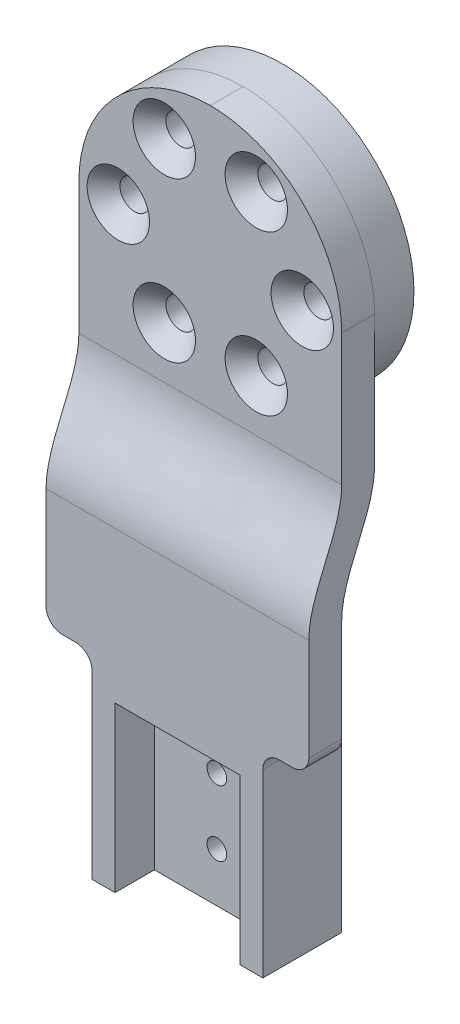
SolidWorks part; units mm, degrees
other "Markup1"
sketch "Sketch13" plane through (20, -53, 11) normal (0.0614, -0.6805, 0.7302) x (0.9699, -0.1321, -0.2046)
ref_plane "Front Plane" through (0, 0, 0) normal (0, 0, 1) x (1, 0, 0)
ref_plane "Top Plane" through (0, 0, 0) normal (0, 1, 0) x (1, 0, 0)
ref_plane "Right Plane" through (0, 0, 0) normal (1, 0, 0) x (0, 0, -1)
sketch "Sketch7" plane through (0, 0, 0) normal (0, 0, 1) x (1, 0, 0)
  line L1 (-20, 20) -> (20, 20)
  line L2 (-20, 20) -> (-20, -20)
  line L3 (-20, -20) -> (20, -20)
  line L4 (20, 20) -> (20, -20)
  line L5 (-20, 20) -> (20, -20) construction
  line L6 (-20, -20) -> (20, 20) construction
  point P0 (0, 0)
extrude "Boss-Extrude1" add sketch "Sketch7" along normal blind 11
ref_plane "Plane2" through (0, -21.4103, 5.7369) normal (0, -0.9659, 0.2588) x (1, 0, 0)
sketch "Sketch8" plane through (0, -20, 2.0782) normal (0, -1, 0) x (1, 0, 0)
  line L0 (20, 8.9218) -> (20, -2.0782) construction
  line L1 (-20, 8.9218) -> (20, 8.9218)
  line L2 (-20, 8.9218) -> (-20, 3.9218)
  line L3 (-20, 3.9218) -> (20, 3.9218)
  line L4 (20, 8.9218) -> (20, 3.9218)
  line L5 (0, 3.9218) -> (0, 8.9218) construction
  line L6 (-20, 6.4218) -> (20, 6.4218) construction
  line L7 (-20, -2.0782) -> (20, -2.0782) construction
  point P764 (0, 6.4218)
  dimension "D1" = 6
ref_plane "Plane4" through (0, -38, 0) normal (0, -1, 0) x (-1, 0, 0)
sketch "Sketch19" plane through (0, -38, 0) normal (0, -1, 0) x (-1, 0, 0)
  line L0 (20, -11) -> (20, 0) construction
  line L1 (20, -16) -> (-20, -16)
  line L2 (20, -16) -> (20, -11)
  line L3 (20, -11) -> (-20, -11)
  line L4 (-20, -16) -> (-20, -11)
  line L5 (20, -16) -> (-20, -11) construction
  line L6 (20, -11) -> (-20, -16) construction
  line L7 (-20, -11) -> (-20, 0) construction
  line L8 (20, -11) -> (-20, -11) construction
  point P4 (0, -13.5)
  dimension "D1" = 5
  dimension "D2" = 5
loft "Loft1" add profiles "Sketch19", "Sketch8" start constraint normal to profile start tangent length 1 end constraint normal to profile end tangent length 1 connector at (-20, -38, 16) connector at (-20, -20, 11)
sketch "Sketch16" plane through (0, 0, 0) normal (0, 0, -1) x (-1, 0, 0)
  line L1 (24.5131, 32.6211) -> (-24.5131, 32.6211)
  line L2 (24.5131, 32.6211) -> (24.5131, -32.6211)
  line L3 (24.5131, -32.6211) -> (-24.5131, -32.6211)
  line L4 (-24.5131, 32.6211) -> (-24.5131, -32.6211)
  line L5 (24.5131, 32.6211) -> (-24.5131, -32.6211) construction
  line L6 (24.5131, -32.6211) -> (-24.5131, 32.6211) construction
  circle A0 centre (0, 0) radius 20
extrude "Cut-Extrude3" cut sketch "Sketch16" against normal blind 6
ref_plane "Plane3" [suppressed] through (0, -56, 0) normal (0, -1, 0) x (-1, 0, 0)
sketch "Sketch17" plane through (0, -38, 0) normal (0, -1, 0) x (-1, 0, 0)
  line L1 (20, -16) -> (-20, -16)
  line L2 (20, -16) -> (20, -11)
  line L3 (20, -11) -> (-20, -11)
  line L4 (-20, -16) -> (-20, -11)
  line L5 (20, -16) -> (-20, -11) construction
  line L6 (20, -11) -> (-20, -16) construction
  line L10 (-20, -16) -> (20, -16) construction
  line L11 (-20, -6) -> (-20, -11) construction
  line L12 (20, -11) -> (20, -6) construction
  point P4 (0, -13.5)
  dimension "D1" = 5
extrude "Boss-Extrude5" add sketch "Sketch17" along normal blind 18
sketch "Sketch10" plane through (0, 0, 11) normal (0, 0, 1) x (1, 0, 0)
  circle A0 centre (-7.0001, 12.1244) radius 2.25
  circle A1 centre (6.9999, 12.1244) radius 2.25
  circle A2 centre (13.9999, 0.0001) radius 2.25
  circle A3 centre (6.9999, -12.1243) radius 2.25
  circle A4 centre (-7.0001, -12.1243) radius 2.25
  circle A5 centre (-14.0001, 0.0001) radius 2.25
  point P0 (0, 0)
  point P1 (0.0025, 0.0011)
  dimension "D4" = 4.5
extrude "Cut-Extrude1" cut sketch "Sketch10" against normal blind 25
sketch "Sketch11" plane through (0, -56, -3.473) normal (0, 1, 0) x (1, 0, 0)
  line L0 (20, -19.473) -> (-20, -19.473) construction
  line L5 (13, -7.473) -> (-13, -7.473)
  line L6 (13, -7.473) -> (13, -19.473)
  line L7 (13, -19.473) -> (-13, -19.473)
  line L8 (-13, -7.473) -> (-13, -19.473)
  line L9 (13, -7.473) -> (-13, -19.473) construction
  line L10 (13, -19.473) -> (-13, -7.473) construction
  line L12 (-20, -19.473) -> (-20, -14.473) construction
  point P0 (0, -13.473)
  dimension "D1" = 26
  dimension "D2" = 20
  dimension "D3" = 12
chamfer "Chamfer1" distance 2.5 angle 45 6 edges at (-4.7501, 12.1244, 11) (-11.7501, 0.0001, 11) (-4.7501, -12.1243, 11) (9.2499, 12.1244, 11) (16.2499, 0.0001, 11) (9.2499, -12.1243, 11)
fillet "Fillet3" radius 20 2 edges at (20, 20, 8.5) (-20, 20, 8.5)
extrude "Boss-Extrude6" add sketch "Sketch11" against normal blind 30
ref_plane "Plane5" through (0, -86, 0) normal (0, -1, 0) x (-1, 0, 0)
sketch "Sketch21" plane through (0, -86, 0) normal (0, -1, 0) x (-1, 0, 0)
  line L0 (13, -16) -> (-13, -16) construction
  line L1 (-9.5, -10) -> (9.5, -10)
  line L2 (-9.5, -10) -> (-9.5, -16)
  line L3 (-9.5, -16) -> (9.5, -16)
  line L4 (9.5, -10) -> (9.5, -16)
  line L5 (-9.5, -10) -> (9.5, -16) construction
  line L6 (-9.5, -16) -> (9.5, -10) construction
  line L7 (13, -4) -> (13, -16) construction
  point P0 (0, -13)
  dimension "D1" = 6
  dimension "D2" = 19
  dimension "D3" = 13
extrude "Cut-Extrude4" cut sketch "Sketch21" against normal blind 25
fillet "Fillet5" radius 2.5 4 edges at (-13, -56, 13.5) (-20, -56, 13.5) (13, -56, 13.5) (20, -56, 13.5)
fillet "Fillet7" radius 2.5 2 edges at (0, -56, 11) (0, -56, 4)
sketch "Sketch22" plane through (0, 0, 0) normal (0, 0, 1) x (1, 0, 0)
  line L0 (13, -86) -> (13, -58.5) construction
  line L1 (-17.6217, -73.5) -> (22.5957, -73.5) construction
  line L2 (-6.6, -86) -> (6.6, -86) construction
  circle A0 centre (0, -68.5) radius 1.5
  circle A1 centre (0, -78.5) radius 1.5
  dimension "D1" = 3
  dimension "D2" = 3
  dimension "D3" = 10
  dimension "D4" = 13
  dimension "D5" = 5
  dimension "D6" = 12.5
extrude "Cut-Extrude5" cut sketch "Sketch22" against normal mid plane 25
